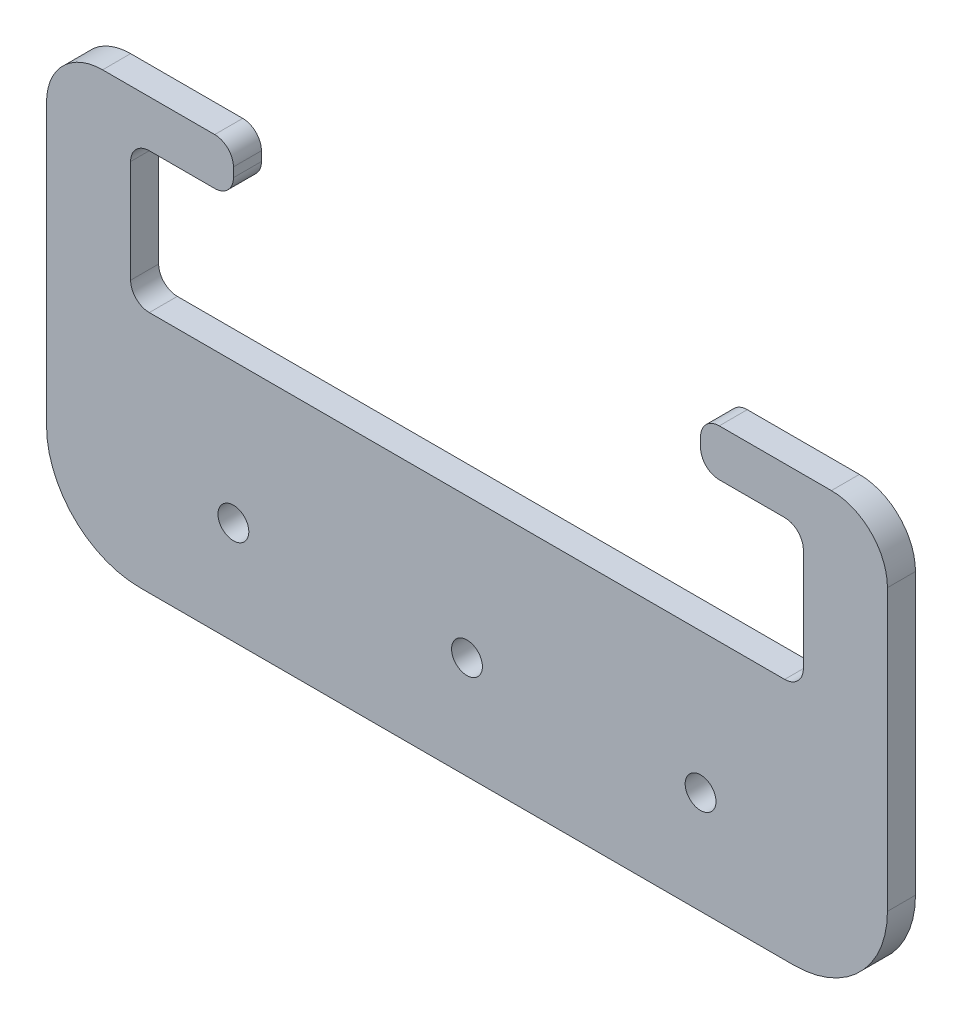
SolidWorks part; units mm, degrees
material "Thornel Mat VMA"
ref_plane "前视基准面" through (0, 0, 0) normal (0, 0, 1) x (1, 0, 0)
ref_plane "上视基准面" through (0, 0, 0) normal (0, 1, 0) x (1, 0, 0)
ref_plane "右视基准面" through (0, 0, 0) normal (1, 0, 0) x (0, 0, -1)
other "Configuration Table"
sketch "草图1" plane through (0, 0, 0) normal (0, 0, 1) x (1, 0, 0)
  line L0 (25, 25) -> (45, 25)
  line L1 (-45, 25) -> (-25, 25)
  line L2 (-45, 25) -> (-45, -25)
  line L3 (-45, -25) -> (45, -25)
  line L4 (45, 25) -> (45, -25)
  line L5 (-45, 25) -> (45, -25) construction
  line L6 (-45, -25) -> (45, 25) construction
  line L8 (25, 25) -> (25, 20)
  line L10 (-25, 25) -> (-25, 20)
  line L11 (36, 20) -> (25, 20)
  line L12 (36, 20) -> (36, 5)
  line L13 (36, 5) -> (-36, 5)
  line L14 (-36, 20) -> (-36, 5)
  line L15 (-25, 20) -> (-36, 20)
  point P0 (0, 0)
  dimension "D1" = 50
  dimension "D2" = 90
  dimension "D3" = 5
  dimension "D4" = 20
  dimension "D5" = 20
  dimension "D6" = 9
  dimension "D7" = 9
  dimension "D8" = 15
extrude "凸台-拉伸1" add sketch "草图1" along normal blind 3
fillet "圆角1" radius 6 2 edges at (45, 25, 1.5) (-45, 25, 1.5)
fillet "圆角2" radius 2 8 edges at (36, 20, 1.5) (36, 5, 1.5) (-36, 5, 1.5) (-36, 20, 1.5) (-25, 20, 1.5) (-25, 25, 1.5) (25, 20, 1.5) (25, 25, 1.5)
sketch "草图2" plane through (0, 0, 3) normal (0, 0, 1) x (1, 0, 0)
  line L0 (-45, -25) -> (45, -25) construction
  line L2 (0, 12.1144) -> (0, -26.36) construction
  circle A0 centre (-25, -10) radius 1.65
  circle A1 centre (25, -10) radius 1.65
  circle A2 centre (0, -10) radius 1.65
  dimension "D1" = 3.3
  dimension "D2" = 3.3
  dimension "D6" = 25
  dimension "D5" = 25
  dimension "D7" = 3.3
  dimension "D8" = 15
  dimension "D3" = 15
  dimension "D4" = 15
extrude "切除-拉伸1" cut sketch "草图2" against normal blind 5
fillet "圆角3" radius 10 2 edges at (-45, -25, 1.5) (45, -25, 1.5)
sketch "草图3" plane through (0, 0, 3) normal (0, 0, 1) x (1, 0, 0)
  line L0 (-35, -25) -> (35, -25) construction
  line L1 (-45, -25) -> (45, -25)
  line L2 (-45, -25) -> (-45, -21)
  line L3 (-45, -21) -> (45, -21)
  line L4 (45, -25) -> (45, -21)
  line L5 (45, -15) -> (45, 19) construction
  line L6 (-45, 19) -> (-45, -15) construction
  dimension "D1" = 4
extrude "切除-拉伸2" cut sketch "草图3" against normal blind 10
fillet "圆角4" radius 10 2 edges at (43, -21, 1.5) (-43, -21, 1.5)
